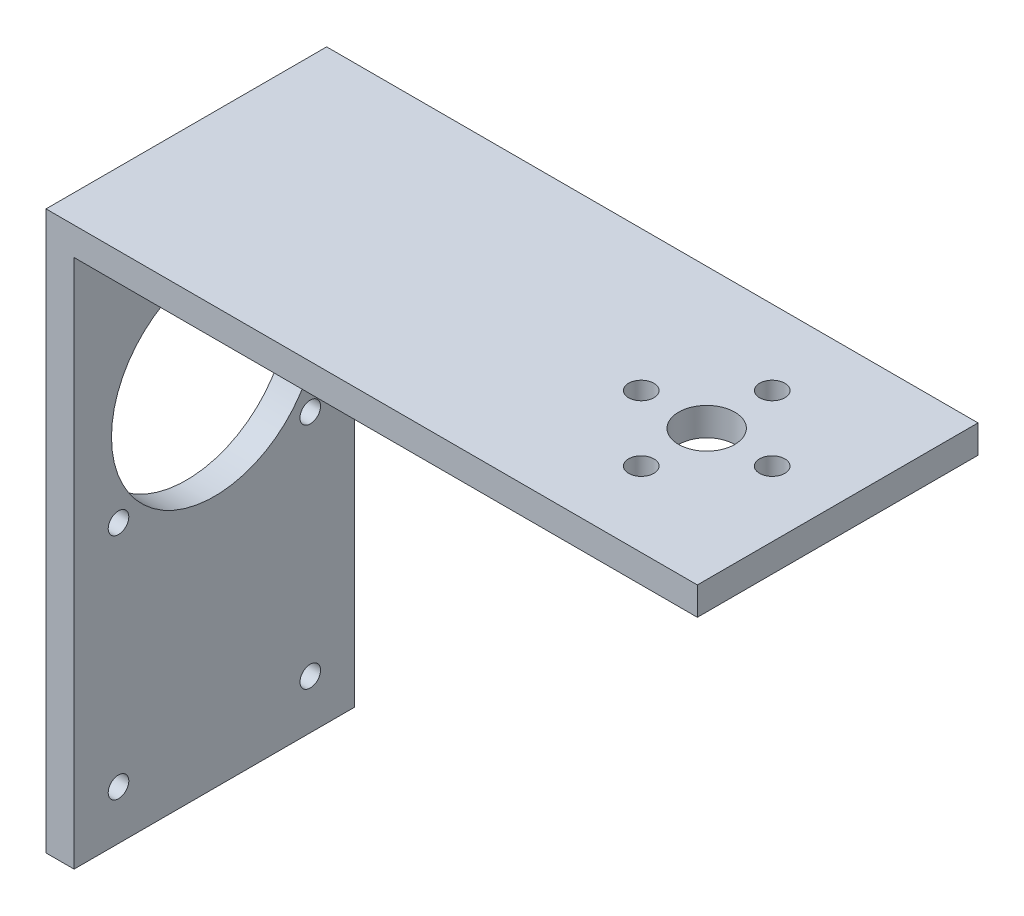
SolidWorks part; units mm, degrees
ref_plane "Front Plane" through (0, 0, 0) normal (0, 0, 1) x (1, 0, 0)
ref_plane "Top Plane" through (0, 0, 0) normal (0, 1, 0) x (1, 0, 0)
ref_plane "Right Plane" through (0, 0, 0) normal (1, 0, 0) x (0, 0, -1)
ref_plane "PZ_m15_000" through (0, 0, -15) normal (0, 0, 1) x (1, 0, 0)
sketch "S_box1" plane through (0, 0, -15) normal (0, 0, 1) x (1, 0, 0)
  line L0 (-55.625, 18.625) -> (14, 18.625)
  line L1 (14, 18.625) -> (14, 21.625)
  line L2 (14, 21.625) -> (-55.625, 21.625)
  line L3 (-55.625, 21.625) -> (-55.625, 18.625)
  dimension "P1" = 55.625
  dimension "P2" = 18.625
  dimension "P3" = 14
  dimension "P4" = 18.625
  dimension "P5" = 14
  dimension "P6" = 21.625
  dimension "P7" = 55.625
  dimension "P8" = 21.625
extrude "Boss_1" add sketch "S_box1" along normal blind 30
sketch "S_box2" plane through (0, 0, -15) normal (0, 0, 1) x (1, 0, 0)
  line L0 (-55.625, -38) -> (-52.625, -38)
  line L1 (-52.625, -38) -> (-52.625, 19.125)
  line L2 (-52.625, 19.125) -> (-55.625, 19.125)
  line L3 (-55.625, 19.125) -> (-55.625, -38)
  dimension "P1" = 55.625
  dimension "P2" = 38
  dimension "P3" = 52.625
  dimension "P4" = 38
  dimension "P5" = 52.625
  dimension "P6" = 19.125
  dimension "P7" = 55.625
  dimension "P8" = 19.125
extrude "Boss_2" add sketch "S_box2" along normal blind 30
sketch "S_box3" plane through (0, 0, -15) normal (0, 0, 1) x (1, 0, 0)
  line L0 (-53.125, 15.625) -> (-24, 15.625)
  line L1 (-24, 15.625) -> (-24, 19.125)
  line L2 (-24, 19.125) -> (-53.125, 19.125)
  line L3 (-53.125, 19.125) -> (-53.125, 15.625)
  dimension "P1" = 53.125
  dimension "P2" = 15.625
  dimension "P3" = 24
  dimension "P4" = 15.625
  dimension "P5" = 24
  dimension "P6" = 19.125
  dimension "P7" = 53.125
  dimension "P8" = 19.125
extrude "Boss_3" add sketch "S_box3" along normal blind 3
ref_plane "PY_p18_525" through (0, 18.525, 0) normal (0, 1, 0) x (1, 0, 0)
sketch "S_hole4" plane through (0, 18.525, 0) normal (0, 1, 0) x (1, 0, 0)
  circle A0 centre (0, 0) radius 3
  dimension "D1_S_hole4" = 6
extrude "Hole_4" cut sketch "S_hole4" along normal blind 3.2
sketch "S_hole5" plane through (0, 18.525, 0) normal (0, 1, 0) x (1, 0, 0)
  circle A0 centre (7, 0) radius 1.35
  dimension "D1_S_hole5" = 2.7
  dimension "P2" = 7
extrude "Hole_5" cut sketch "S_hole5" along normal blind 3.2
sketch "S_hole6" plane through (0, 18.525, 0) normal (0, 1, 0) x (1, 0, 0)
  circle A0 centre (0, -7) radius 1.35
  dimension "D1_S_hole6" = 2.7
  dimension "P2" = 7
extrude "Hole_6" cut sketch "S_hole6" along normal blind 3.2
sketch "S_hole7" plane through (0, 18.525, 0) normal (0, 1, 0) x (1, 0, 0)
  circle A0 centre (-7, 0) radius 1.35
  dimension "D1_S_hole7" = 2.7
  dimension "P2" = 7
extrude "Hole_7" cut sketch "S_hole7" along normal blind 3.2
sketch "S_hole8" plane through (0, 18.525, 0) normal (0, 1, 0) x (1, 0, 0)
  circle A0 centre (0, 7) radius 1.35
  dimension "D1_S_hole8" = 2.7
  dimension "P2" = 7
extrude "Hole_8" cut sketch "S_hole8" along normal blind 3.2
ref_plane "PX_m55_725" through (-55.725, 0, 0) normal (1, 0, 0) x (0, 0, -1)
sketch "S_hole9" plane through (-55.725, 0, 0) normal (1, 0, 0) x (0, 0, -1)
  circle A0 centre (0, 0) radius 11
  dimension "D1_S_hole9" = 22
extrude "Hole_9" cut sketch "S_hole9" along normal blind 3.2
sketch "S_hole10" plane through (-55.725, 0, 0) normal (1, 0, 0) x (0, 0, -1)
  circle A0 centre (10.25, -8.3) radius 1.1
  dimension "D1_S_hole10" = 2.2
  dimension "P2" = 10.25
  dimension "P3" = 8.3
extrude "Hole_10" cut sketch "S_hole10" along normal blind 3.2
sketch "S_hole11" plane through (-55.725, 0, 0) normal (1, 0, 0) x (0, 0, -1)
  circle A0 centre (-10.25, -8.3) radius 1.1
  dimension "D1_S_hole11" = 2.2
  dimension "P2" = 10.25
  dimension "P3" = 8.3
extrude "Hole_11" cut sketch "S_hole11" along normal blind 3.2
sketch "S_hole12" plane through (-55.725, 0, 0) normal (1, 0, 0) x (0, 0, -1)
  circle A0 centre (10.25, -32.75) radius 1.1
  dimension "D1_S_hole12" = 2.2
  dimension "P2" = 10.25
  dimension "P3" = 32.75
extrude "Hole_12" cut sketch "S_hole12" along normal blind 3.2
sketch "S_hole13" plane through (-55.725, 0, 0) normal (1, 0, 0) x (0, 0, -1)
  circle A0 centre (-10.25, -32.75) radius 1.1
  dimension "D1_S_hole13" = 2.2
  dimension "P2" = 10.25
  dimension "P3" = 32.75
extrude "Hole_13" cut sketch "S_hole13" along normal blind 3.2
equation "\"plate_t\" = 3"
equation "\"clearance\" = 0.4"
